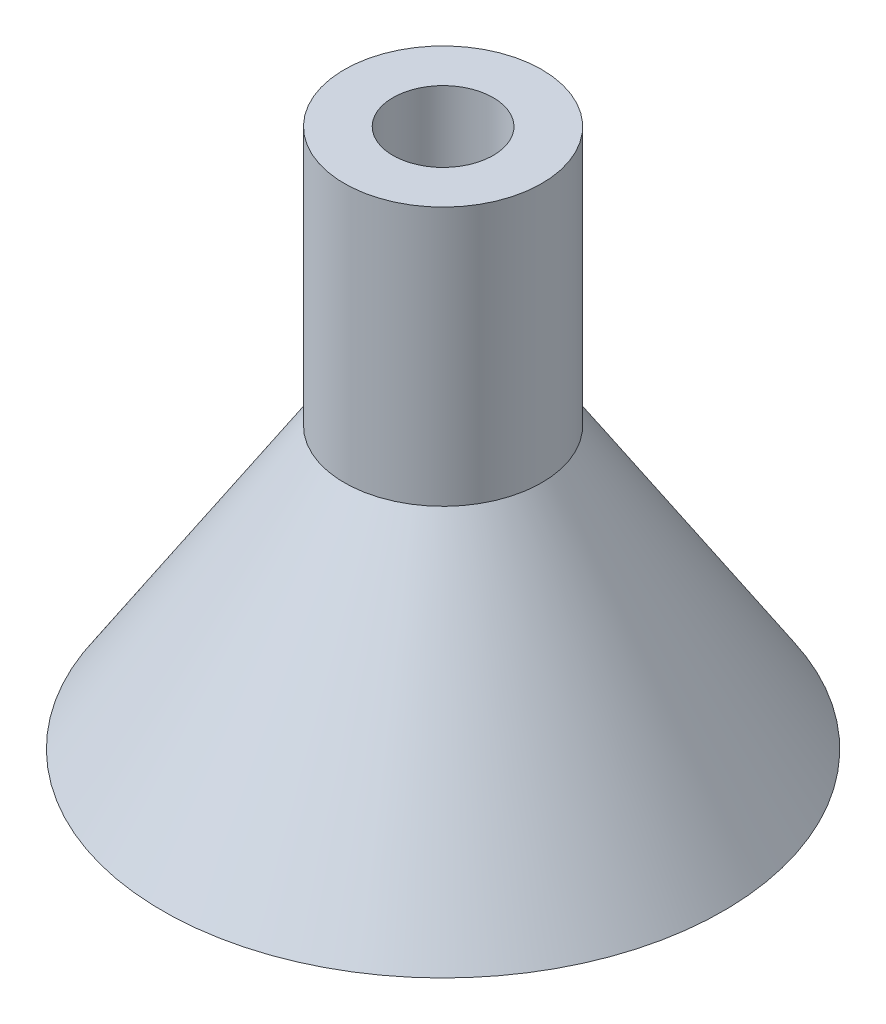
SolidWorks part; units mm, degrees
ref_plane "Front Plane" through (0, 0, 0) normal (0, 0, 1) x (1, 0, 0)
ref_plane "Top Plane" through (0, 0, 0) normal (0, 1, 0) x (1, 0, 0)
ref_plane "Right Plane" through (0, 0, 0) normal (1, 0, 0) x (0, 0, -1)
sketch "Sketch2" plane through (0, 0, 0) normal (0, 0, 1) x (1, 0, 0)
  line L0 (14.2198, 0) -> (17.3199, 0)
  line L1 (17.3199, 0) -> (6.096, 17.2833)
  line L2 (6.096, 17.2833) -> (6.096, 33.2833)
  line L3 (6.096, 33.2833) -> (3.096, 33.2833)
  line L4 (3.096, 33.2833) -> (3.096, 17.1291)
  line L5 (3.096, 17.1291) -> (14.2198, 0)
  line L6 (0, 0) -> (0, 50000) construction
  line L7 (-3.096, 17.1291) -> (-14.2198, 0) construction
  line L8 (-3.096, 33.2833) -> (-3.096, 17.1291) construction
  line L9 (-6.096, 33.2833) -> (-3.096, 33.2833) construction
  line L10 (-6.096, 17.2833) -> (-6.096, 33.2833) construction
  line L11 (-17.3199, 0) -> (-6.096, 17.2833) construction
  line L12 (-14.2198, 0) -> (-17.3199, 0) construction
  dimension "D1" = 3
  dimension "D2" = 2.6
  dimension "D3" = 12.192
  dimension "D5" = 16
  dimension "D6" = 33
revolve "Revolve1" add sketch "Sketch2" angle 360 about L6
